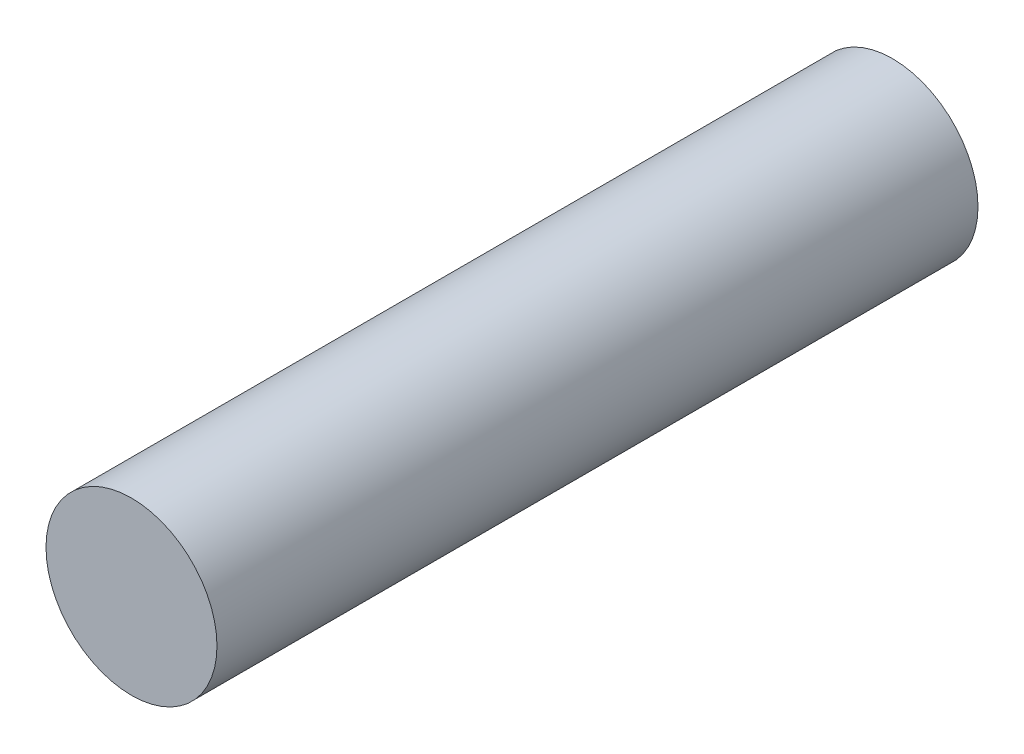
SolidWorks part; units mm, degrees
ref_plane "前视基准面" through (0, 0, 0) normal (0, 0, 1) x (1, 0, 0)
ref_plane "上视基准面" through (0, 0, 0) normal (0, 1, 0) x (1, 0, 0)
ref_plane "右视基准面" through (0, 0, 0) normal (1, 0, 0) x (0, 0, -1)
sketch "草图1" plane through (0, 0, 0) normal (0, 0, 1) x (1, 0, 0)
  circle A0 centre (0, 0) radius 3.37
extrude "凸台-拉伸1" add sketch "草图1" along normal blind 30
